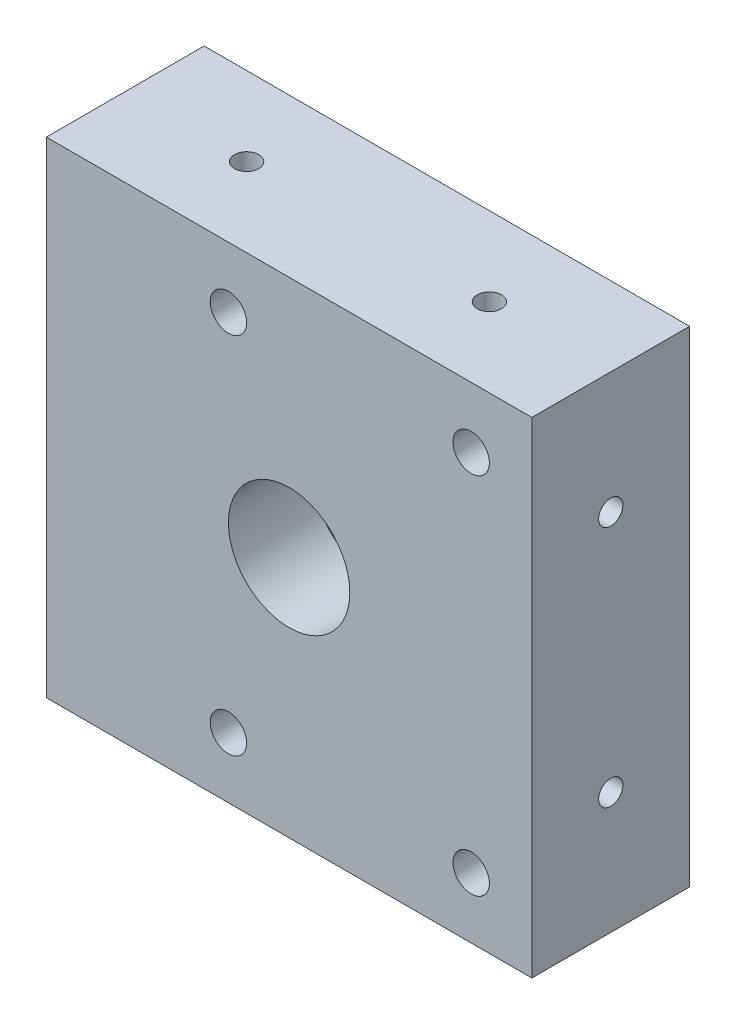
SolidWorks part; units mm, degrees
material "PET"
ref_plane "Front Plane" through (0, 0, 0) normal (1, 0, 0) x (0, 1, 0)
ref_plane "Top Plane" through (0, 0, 0) normal (0, 0, 1) x (0, 1, 0)
ref_plane "Right Plane" through (0, 0, 0) normal (0, 1, 0) x (-1, 0, 0)
sketch "Sketch1" plane through (0, 0, 0) normal (0, 0, 1) x (0, 1, 0)
  line L1 (-20, -20) -> (20, -20)
  line L2 (-20, -20) -> (-20, 20)
  line L3 (-20, 20) -> (20, 20)
  line L4 (20, -20) -> (20, 20)
  line L5 (-20, -20) -> (20, 20) construction
  line L6 (-20, 20) -> (20, -20) construction
  line L7 (-5, 5) -> (5, 5)
  line L8 (-5, 5) -> (-5, -5)
  line L9 (-5, -5) -> (5, -5)
  line L10 (5, 5) -> (5, -5)
  line L11 (-5, 5) -> (5, -5) construction
  line L12 (-5, -5) -> (5, 5) construction
  line L13 (5, -5) -> (-5, -5)
  line L14 (5, -5) -> (5, -13)
  line L15 (5, -13) -> (-5, -13)
  line L16 (-5, -5) -> (-5, -13)
  line L17 (-5, -13) -> (-8, -13)
  line L18 (-5, -13) -> (-5, -5)
  line L19 (-5, -5) -> (-8, -5)
  line L20 (-8, -13) -> (-8, -5)
  circle A0 centre (-10.5, 0) radius 0.9
  circle A1 centre (-10.5, 12.5) radius 0.9
  circle A2 centre (10.5, 0) radius 0.9
  circle A3 centre (10.5, 12.5) radius 0.9
  point P0 (0, 0)
  point P6 (0, 0)
  dimension "D4" = 8
  dimension "D1" = 40
  dimension "D2" = 40
  dimension "D3" = 10
  dimension "D5" = 3
extrude "Boss-Extrude1" add sketch "Sketch1" along normal blind 6 contours L1 L4 L3 L2 A2 A1 A0 L17 L20 L19 L8 L7 L10 L14 L15 A3 region at (0, -19.4343, 0)
sketch "Sketch11" plane through (0, 0, 6) normal (0, 0, 1) x (1, 0, 0)
  line L1 (-20, 20) -> (20, 20)
  line L2 (-20, 20) -> (-20, -20)
  line L3 (-20, -20) -> (20, -20)
  line L4 (20, 20) -> (20, -20)
  circle A0 centre (0, 0) radius 5
extrude "Boss-Extrude6" add sketch "Sketch11" along normal blind 7
sketch "Sketch13" plane through (0, 0, 0) normal (0, 0, -1) x (1, 0, 0)
  line L5 (-10, -17.5) -> (10, 17.5) construction
  line L6 (-10, 17.5) -> (10, -17.5) construction
  circle A0 centre (-6.25, 13.75) radius 1.5
  circle A1 centre (6.25, 13.75) radius 1.5
  circle A2 centre (6.25, -13.75) radius 1.5
  circle A3 centre (-6.25, -13.75) radius 1.5
  circle A4 centre (-6.25, 13.75) radius 3
  circle A5 centre (6.25, 13.75) radius 3
  circle A6 centre (-6.25, -13.75) radius 3
  circle A7 centre (6.25, -13.75) radius 1.3954
  circle A8 centre (6.25, -13.75) radius 3
  point P0 (0, 0)
  dimension "D1" = 20
  dimension "D2" = 35
  dimension "D3" = 2
  dimension "D4" = 2
extrude "Cut-Extrude5" cut sketch "Sketch13" against normal blind 27 contours A0 | A1 | A7 | A3 region at (-6.25, -13.75, 0) region at (6.25, -13.75, 0) region at (-6.25, 13.75, 0) region at (6.25, 13.75, 0)
extrude "Cut-Extrude6" cut sketch "Sketch13<3>" against normal blind 3 contours A6 A3 | A5 A1 | A4 A0 | A8 region at (-9.1651, -13.75, 0) region at (3.3349, -13.75, 0) region at (-9.1651, 13.75, 0)
sketch "Sketch13<3>" plane through (0, 0, 0) normal (0, 0, -1) x (1, 0, 0) same geometry as "Sketch13"
sketch "Sketch15" plane through (0, 20, 0) normal (0, 1, 0) x (-1, 0, 0)
  circle A0 centre (-13.5, 6.5) radius 2.5
  circle A1 centre (13.5, 6.5) radius 2.5
extrude "Cut-Extrude9" cut sketch "Sketch15" against normal blind 5
pattern_circular "CirPattern4" count 4 every 90 about axis through (0, 0, 13) along (0, 0, 1) of "Cut-Extrude9"
sketch "Sketch16" plane through (0, 0, 0) normal (0, 0, -1) x (1, 0, 0)
  circle A0 centre (-6.25, 13.75) radius 3
  circle A1 centre (6.25, 13.75) radius 3
  circle A2 centre (-6.25, -13.75) radius 3
  circle A3 centre (6.25, -13.75) radius 3
extrude "Boss-Extrude7" add sketch "Sketch16" against normal up to surface (13 mm away) up to face at (-4.75, 13.75, 13)
sketch "Sketch17" plane through (0, 20, 0) normal (0, 1, 0) x (-1, 0, 0)
  circle A0 centre (-13.5, 6.5) radius 2.5
  circle A1 centre (13.5, 6.5) radius 2.5
extrude "Boss-Extrude8" add sketch "Sketch17" against normal up to surface (5 mm away) up to face at (13, 15, 6.5)
sketch "Sketch18" plane through (-20, 0, 0) normal (-1, 0, 0) x (0, -1, 0)
  circle A0 centre (-13.5, 6.5) radius 2.5
  circle A1 centre (13.5, 6.5) radius 2.5
extrude "Boss-Extrude9" add sketch "Sketch18" against normal up to surface (5 mm away) up to face at (-15, 13, 6.5)
sketch "Sketch19" plane through (0, -20, 0) normal (0, -1, 0) x (1, 0, 0)
  circle A0 centre (-13.5, 6.5) radius 2.5
  circle A1 centre (13.5, 6.5) radius 2.5
extrude "Boss-Extrude10" add sketch "Sketch19" against normal up to surface (5 mm away) up to face at (-13, -15, 6.5)
sketch "Sketch20" plane through (20, 0, 0) normal (1, 0, 0) x (0, 1, 0)
  circle A0 centre (-13.5, 6.5) radius 2.5
  circle A1 centre (13.5, 6.5) radius 2.5
extrude "Boss-Extrude11" add sketch "Sketch20" against normal up to surface (5 mm away) up to face at (15, -13, 6.5)
sketch "Sketch21" plane through (0, 0, 0) normal (0, 0, -1) x (1, 0, 0)
  line L0 (20, -20) -> (-20, -20) construction
  line L1 (20, 20) -> (-10, 20)
  line L2 (20, 20) -> (20, -20)
  line L3 (20, -20) -> (-10, -20)
  line L4 (-10, 20) -> (-10, -20)
  circle A0 centre (-5, 15) radius 2.5
  circle A2 centre (15, 15) radius 2.5
  circle A3 centre (15, -15) radius 2.5
  circle A4 centre (-5, -15) radius 2.5
  circle A5 centre (-5, 15) radius 1.5
  circle A6 centre (15, 15) radius 1.5
  circle A7 centre (-5, -15) radius 1.5
  circle A8 centre (15, -15) radius 1.5
  dimension "D1" = 30
  dimension "D2" = 2
  dimension "D3" = 2
extrude "Cut-Extrude10" cut sketch "Sketch21" against normal blind 25 contours A5 | A6 | A8 | A7 region at (-5, -15, 0) region at (15, -15, 0) region at (-5, 15, 0) region at (15, 15, 0)
extrude "Cut-Extrude11" cut sketch "Sketch21<3>" against normal blind 5 contours A0 A5 | A2 A6 | A3 A8 | A4 A7 region at (-7.4293, -15, 0) region at (12.5707, -15, 0) region at (12.5707, 15, 0) region at (-7.4293, 15, 0)
sketch "Sketch21<3>" plane through (0, 0, 0) normal (0, 0, -1) x (1, 0, 0) same geometry as "Sketch21"
sketch "Sketch22" plane through (0, 20, 0) normal (0, 1, 0) x (-1, 0, 0)
  circle A0 centre (-10, 6.5) radius 1
  circle A1 centre (10, 6.5) radius 1
extrude "Cut-Extrude12" cut sketch "Sketch22" against normal blind 7
pattern_circular "CirPattern5" count 4 every 90 about axis through (0, 0, 13) along (0, 0, 1) of "Cut-Extrude12"
